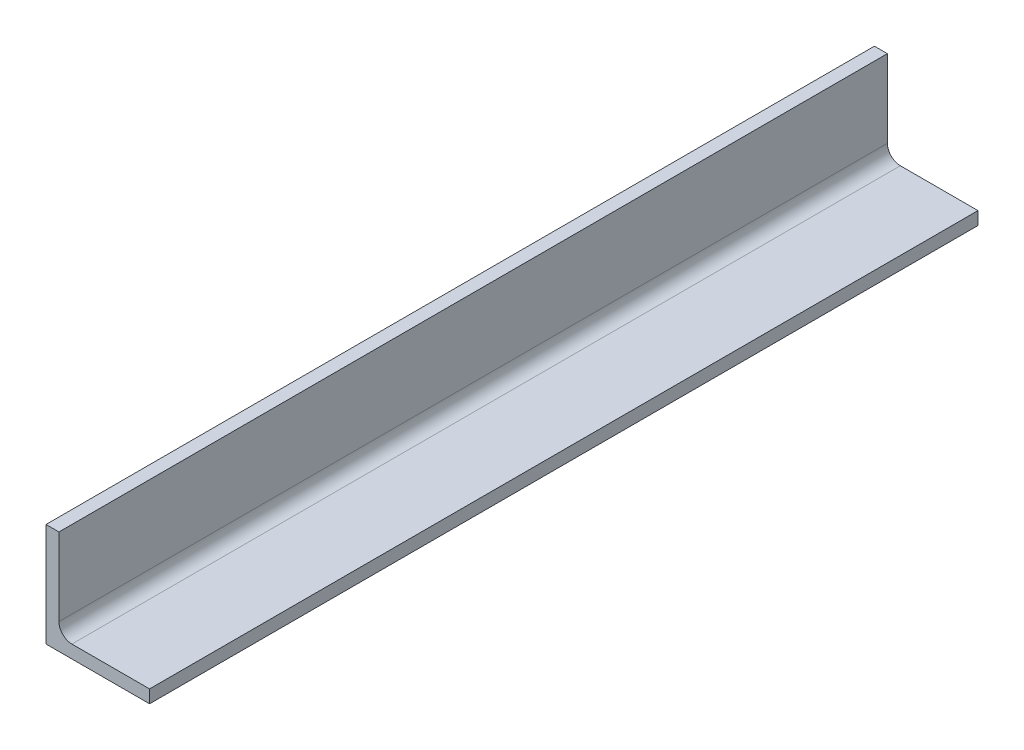
SolidWorks part; units mm, degrees
ref_plane "Front Plane" through (0, 0, 0) normal (0, 0, 1) x (1, 0, 0)
ref_plane "Top Plane" through (0, 0, 0) normal (0, 1, 0) x (1, 0, 0)
ref_plane "Right Plane" through (0, 0, 0) normal (1, 0, 0) x (0, 0, -1)
sketch "Sketch2" plane through (0, 0, 0) normal (0, 0, 1) x (1, 0, 0)
  line L0 (0, 0) -> (0, 50.8)
  line L1 (0, 50.8) -> (6.35, 50.8)
  line L2 (6.35, 50.8) -> (6.35, 12.7)
  line L3 (12.7, 6.35) -> (50.8, 6.35)
  line L4 (50.8, 6.35) -> (50.8, 0)
  line L5 (50.8, 0) -> (0, 0)
  arc A0 (12.7, 6.35) -> (6.35, 12.7) centre (12.7, 12.7) cw
  dimension "D4" = 6.35
  dimension "D1" = 6.35
  dimension "D2" = 50.8
  dimension "D3" = 50.8
extrude "Boss-Extrude1" add sketch "Sketch2" along normal mid plane 406.4
